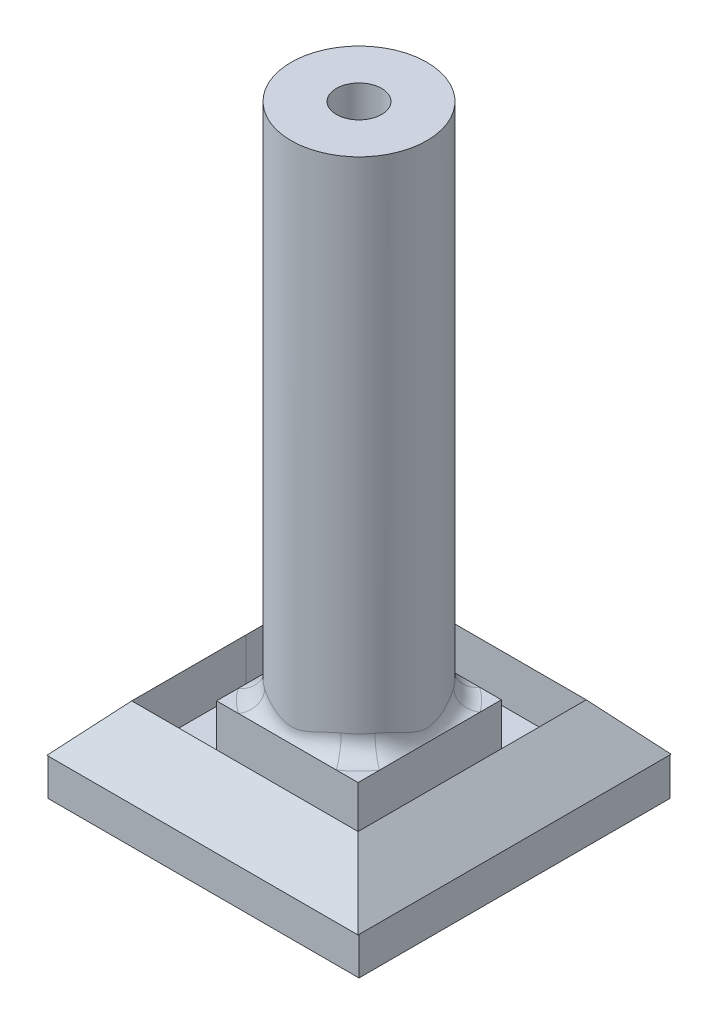
SolidWorks part; units mm, degrees
ref_plane "Front Plane" through (0, 0, 0) normal (0, 0, 1) x (1, 0, 0)
ref_plane "Top Plane" through (0, 0, 0) normal (0, 1, 0) x (1, 0, 0)
ref_plane "Right Plane" through (0, 0, 0) normal (1, 0, 0) x (0, 0, -1)
sketch "Sketch1" plane through (0, 0, 0) normal (0, 1, 0) x (1, 0, 0)
  line L1 (16.5, -16.5) -> (-16.5, -16.5)
  line L2 (16.5, -16.5) -> (16.5, 16.5)
  line L3 (16.5, 16.5) -> (-16.5, 16.5)
  line L4 (-16.5, -16.5) -> (-16.5, 16.5)
  line L5 (16.5, -16.5) -> (-16.5, 16.5) construction
  line L6 (16.5, 16.5) -> (-16.5, -16.5) construction
  circle A1 centre (0, 0) radius 5
  point P0 (0, 0)
  dimension "D1" = 33
  dimension "D2" = 33
extrude "Boss-Extrude1" add sketch "Sketch1" along normal blind 4
sketch "Sketch2" plane through (0, 0, 0) normal (0, 0, 1) x (1, 0, 0)
  line L0 (-12, 4) -> (-16.5, 4)
  line L1 (-16.5, 4) -> (16.5, 4) construction
  line L2 (-16.5, 4) -> (-12, 9)
  line L3 (-12, 9) -> (-12, 4)
  dimension "D1" = 4.5
  dimension "D4" = 5
ref_axis "Axis1" through (0, 7.35, 0) along (0, -1, 0)
sketch "Sketch3" plane through (0, 4, 0) normal (0, 1, 0) x (1, 0, 0)
  line L0 (16.5, 16.5) -> (-16.5, 16.5) construction
  line L1 (12, -12.1) -> (-12, -12.1)
  line L2 (12, -12.1) -> (12, 12.1)
  line L3 (12, 12.1) -> (-12, 12.1)
  line L4 (-12, -12.1) -> (-12, 12.1)
  line L5 (12, -12.1) -> (-12, 12.1) construction
  line L6 (12, 12.1) -> (-12, -12.1) construction
  point P0 (0, 0)
  dimension "D1" = 4.4
sweep "Sweep1" add profiles "Sketch2" path "Sketch3"
sketch "Sketch4" plane through (0, 0, 0) normal (0, 0, 1) x (1, 0, 0)
  line L0 (-7.5, 9) -> (-7.5, 4)
  line L1 (-12, 9) -> (12, 9) construction
  line L2 (-12, 4) -> (12, 4) construction
  line L3 (-7.5, 4) -> (-4.5021, 4.1111)
  line L4 (16.4, 4.1111) -> (-16.4, 4.1111) construction
  line L5 (-4.5021, 4.1111) -> (-7.5, 9)
  line L6 (-12, 9) -> (-12, 4) construction
  dimension "D1" = 4.5
  dimension "D2" = 3
sketch "Sketch5" plane through (0, 4, 0) normal (0, 1, 0) x (1, 0, 0)
  line L1 (7.5, -7.6) -> (-7.5, -7.6)
  line L2 (7.5, -7.6) -> (7.5, 7.6)
  line L3 (7.5, 7.6) -> (-7.5, 7.6)
  line L4 (-7.5, -7.6) -> (-7.5, 7.6)
  line L5 (7.5, -7.6) -> (-7.5, 7.6) construction
  line L6 (7.5, 7.6) -> (-7.5, -7.6) construction
  line L7 (-12, 12.1) -> (12, 12.1) construction
  circle A0 centre (0, 0) radius 5
  point P0 (0, 0)
  dimension "D1" = 4.5
sketch "Sketch6" plane through (0, 4, 0) normal (0, 1, 0) x (1, 0, 0)
  circle A0 centre (0, 0) radius 5
  circle A1 centre (0, 0) radius 7.2
  dimension "D1" = 10
  dimension "D2" = 2.2
extrude "Boss-Extrude4" add sketch "Sketch6" along normal blind 60
sketch "Sketch7" plane through (0, 64, 0) normal (0, 1, 0) x (1, 0, 0)
  circle A0 centre (0, 0) radius 2.3
  circle A1 centre (0, 0) radius 6.2
  circle M3 centre (0, 0) radius 7.2
  circle M4 centre (0, 0) radius 5
extrude "Boss-Extrude6" add sketch "Sketch5" along normal blind 5
fillet "Fillet1" radius 2 1 edges at (0, 9, 7.2)
extrude "Boss-Extrude7" add sketch "Sketch7" against normal blind 6.5 contours A0 M4 | M3 M4 | A0 region at (0, 64, 0) region at (-6.0246, 64, 0) region at (-4.8586, 64, 0)
sketch "Sketch11" plane through (0, 57.5, 0) normal (0, -1, 0) x (1, 0, 0)
  circle A0 centre (0, 0) radius 1.1524
  point P0 (0, 0)
hole_wizard "CSK for M4 Flat Head Machine Screw1" positions "Sketch11" profile "Sketch12" countersink size "M4" standard "ANSI Metric" end condition through all
sketch "Sketch12" plane through (0, 57.5, 0) normal (1, 0, 0) x (0, 0, -1)
  line L0 (0, 0) -> (0, 6.5)
  line L1 (0, 6.5) -> (2.4, 6.5)
  line L2 (2.4, 6.5) -> (2.4, 2.3)
  line L3 (2.4, 2.3) -> (4.7, 0)
  line L5 (4.7, 0) -> (0, 0)
  line L6 (-2.4, 2.3) -> (-4.7, 0) construction
  line L11 (0, -6.35) -> (0, 107.95) construction
  dimension "Thru Hole Dia." = 4.8
  dimension "Thru Hole Depth" = 6.5
  dimension "Near C'Sink Dia." = 9.4
  dimension "Near C'Sink Angle" = 90
